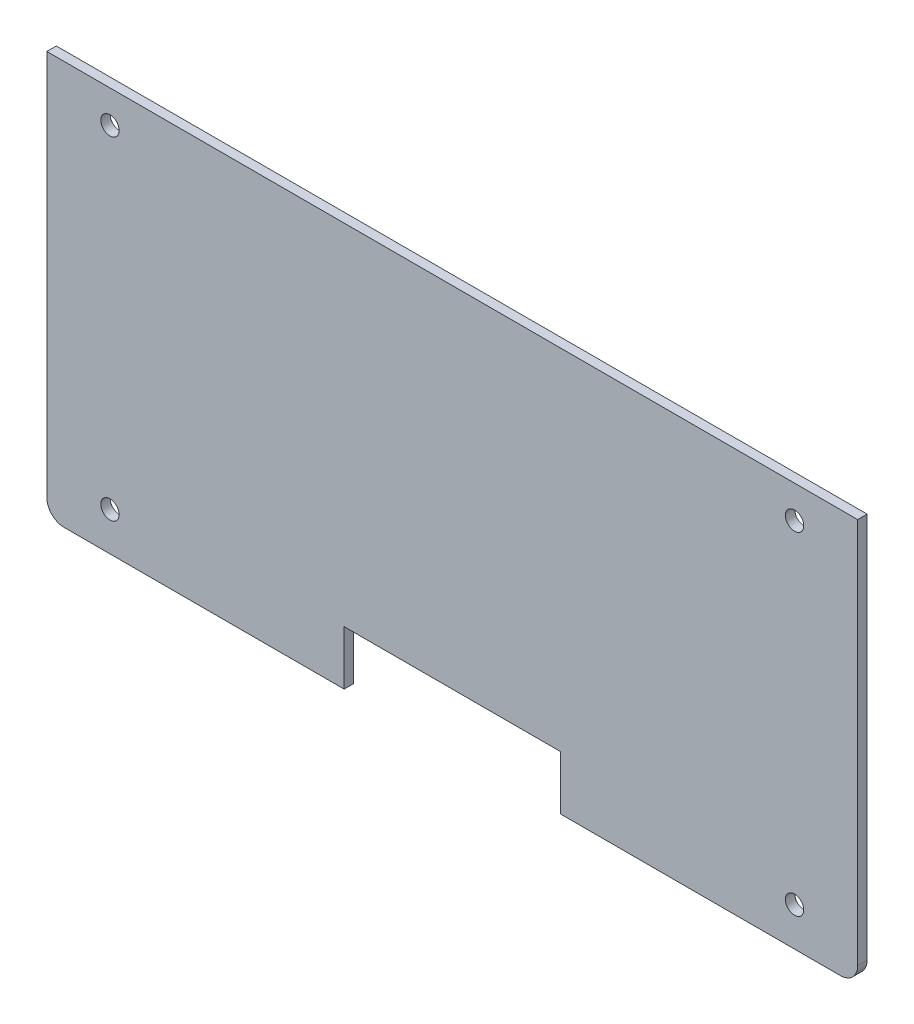
SolidWorks part; units mm, degrees
note: The reader was unsure of these and kept them because the rebuilt part matched: thickness of "Base-Flange1", "Sheet-Metal1", "Sheet-Metal5", "Sheet-Metal8", "Sheet-Metal9".
ref_plane "Front Plane" through (0, 0, 0) normal (0, 0, 1) x (1, 0, 0)
ref_plane "Top Plane" through (0, 0, 0) normal (0, 1, 0) x (1, 0, 0)
ref_plane "Right Plane" through (0, 0, 0) normal (1, 0, 0) x (0, 0, -1)
sketch "Sketch1" plane through (0, 0, 0) normal (0, 0, 1) x (1, 0, 0)
  line L0 (-75, 74.66) -> (75, 74.66) construction
  line L1 (-75, 0) -> (75, 0)
  line L2 (-75, 0) -> (-75, 74.66)
  line L3 (-75, 74.66) -> (75, 74.66)
  line L4 (75, 0) -> (75, 74.66)
  dimension "D1" = 150
base flange "Base-Flange1" sketch "Sketch1" thickness 1.75 reverse thickness direction no parameters "D1"=1.016
sketch "Sketch2" plane through (0, 0, 0) normal (0, 0, 1) x (1, 0, 0)
  line L0 (-75, 0) -> (75, 0) construction
  line L1 (-20, 10) -> (20, 10)
  line L2 (-20, 10) -> (-20, 0)
  line L3 (-20, 0) -> (20, 0)
  line L4 (20, 10) -> (20, 0)
  point P4 (0, 0)
  point P7 (0, 0)
  dimension "D1" = 40
  dimension "D2" = 10
extrude "Cut-Extrude1" cut sketch "Sketch2" against normal up to next normal cut yes
hole_wizard "M3 Clearance Hole1" positions "Sketch5" profile "Sketch6" hole size "M3" standard "ANSI Metric" end condition up to next
sketch "Sketch5" plane through (0, 0, 0) normal (0, 0, 1) x (1, 0, 0)
  point P0 (63.325, 68.66)
  point P3 (63.325, 7.125)
  point P6 (0, 0)
sketch "Sketch6" plane through (63.325, 68.66, 0) normal (1, 0, 0) x (0, -1, 0)
  line L0 (0, 0) -> (0, 1.75)
  line L1 (0, 1.75) -> (1.7, 1.75)
  line L2 (1.7, 1.75) -> (1.7, 0)
  line L5 (1.7, 0) -> (0, 0)
  line L11 (0, -6.35) -> (0, 107.95) construction
  dimension "Thru Hole Dia." = 3.4
  dimension "Thru Hole Depth" = 1.75
mirror "Mirror1" about plane through (0, 0, 0) normal (1, 0, 0) of "M3 Clearance Hole1"
fillet "Fillet1" radius 3.175 2 edges at (-75, 0, -0.875) (75, 0, -0.875)
sketch "Bend-Lines1" [suppressed] plane through (0, 0, 0) normal (0, 1, 0) x (1, 0, 0)
sketch "Bounding-Box1" [suppressed] plane through (0, 0, 0) normal (0, 1, 0) x (1, 0, 0)
sheet metal parameters "Sheet-Metal1" thickness 1.75 parameters "D1"=1.016, "D7"=1.016
flat pattern "Flat-Pattern1" [suppressed]
sketch "Bend-Lines2" plane through (0, 0, 0) normal (0, 1, 0) x (1, 0, 0)
sketch3d "Bounding-Box2" [suppressed]
  line L0 (150, 182.16, 0) -> (150, 0, 0) construction
  line L1 (0, 182.16, 0) -> (0, 0, 0) construction
  line L2 (150, 182.16, 0) -> (0, 182.16, 0) construction
  line L3 (150, 0, 0) -> (0, 0, 0) construction
sheet metal parameters "Sheet-Metal5" thickness 1.75 parameters "D1"=1.016, "D7"=1.016
flat pattern "Flat-Pattern1"
sketch "Bend-Lines2" plane through (0, 0, 0) normal (0, 1, 0) x (1, 0, 0)
sketch3d "Bounding-Box2" [suppressed]
  line L0 (-70.968, 0, 0) -> (70.968, 0, 0) construction
  line L1 (-70.968, 46.25, 0) -> (70.968, 46.25, 0) construction
  line L2 (-70.968, 0, 0) -> (-70.968, 46.25, 0) construction
  line L3 (70.968, 0, 0) -> (70.968, 46.25, 0) construction
sheet metal parameters "Sheet-Metal8" thickness 1.75 parameters "D1"=1.016, "D7"=1.016
flat pattern "Flat-Pattern1"
sketch "Bend-Lines2" plane through (0, 0, 0) normal (0, 1, 0) x (1, 0, 0)
sketch3d "Bounding-Box2" [suppressed]
  line L0 (-75, 0, 0) -> (75, 0, 0) construction
  line L1 (-75, 46.25, 0) -> (75, 46.25, 0) construction
  line L2 (-75, 0, 0) -> (-75, 46.25, 0) construction
  line L3 (75, 0, 0) -> (75, 46.25, 0) construction
sheet metal parameters "Sheet-Metal9" thickness 1.75 parameters "D1"=1.016, "D7"=1.016
flat pattern "Flat-Pattern1"
sketch "Bend-Lines2" plane through (0, 0, 0) normal (0, 1, 0) x (1, 0, 0)
sketch3d "Bounding-Box2" [suppressed]
  line L0 (-74.9999, 74.6602, 0) -> (75, 74.66, 0) construction
  line L1 (-75, 0.0002, 0) -> (74.9999, 0, 0) construction
  line L2 (-74.9999, 74.6602, 0) -> (-75, 0.0002, 0) construction
  line L3 (75, 74.66, 0) -> (74.9999, 0, 0) construction
